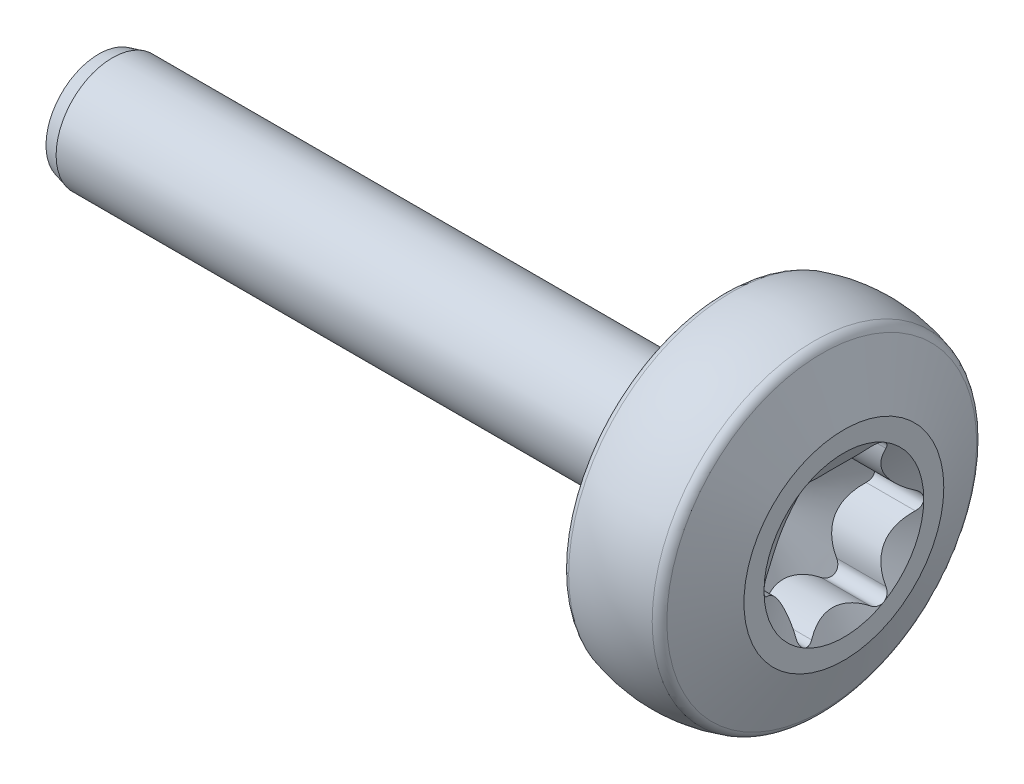
SolidWorks part; units mm, degrees
material "Alloy Steel"
ref_plane "Front Plane" through (0, 0, 0) normal (0, 0, 1) x (1, 0, 0)
ref_plane "Top Plane" through (0, 0, 0) normal (0, 1, 0) x (1, 0, 0)
ref_plane "Right Plane" through (0, 0, 0) normal (1, 0, 0) x (0, 0, -1)
sketch "Sketch1" plane through (0, 0, 0) normal (0, 0, 1) x (1, 0, 0)
  line L0 (-7.5819, 0) -> (7.5819, 0) construction
  line L1 (-7.5819, 1.7526) -> (-7.5819, -1.7526) construction
  line L2 (5.1181, 3.429) -> (5.1181, -3.429) construction
  line L3 (7.5819, 1.6256) -> (7.5819, -1.6256) construction
  line L4 (-8.0147, 1.8973) -> (-7.4298, 0.8843) construction
  line L5 (-7.4298, 0.8843) -> (-8.5996, 0.8843) construction
  line L6 (-8.5996, 0.8843) -> (-8.0147, 1.8973) construction
  line L7 (-8.5996, 0.8843) -> (-8.6831, 0.7396) construction
  line L8 (-8.6831, 0.7396) -> (-7.3463, 0.7396) construction
  line L9 (-7.3463, 0.7396) -> (-7.4298, 0.8843) construction
  line L10 (-8.0983, 1.7526) -> (-7.9312, 1.7526) construction
  line L11 (-8.0147, 1.8973) -> (-8.0147, 1.7526) construction
  line L12 (-8.0147, 0.8843) -> (-8.0147, 0.7396) construction
  point P11 (5.1181, 0)
  point P12 (-7.5819, 1.1477)
  dimension "Screw Size" = 3.5052
  dimension "Torx Diameter" = 3.2512
  dimension "Head Diameter" = 6.858
  dimension "Head Height" = 2.4638
  dimension "Length" = 12.7
  dimension "Thread ID" = 2.2954
  dimension "Approximate Thread Pitch" = 1.3368
  dimension "D1" = 0.1671
sketch "Sketch2" plane through (0, 0, 0) normal (0, 0, 1) x (1, 0, 0)
  line L0 (-7.5819, 0) -> (7.5819, 0)
  line L1 (7.5819, 0) -> (7.5819, 2.0336)
  line L2 (-7.5819, 0) -> (-7.5819, 1.1477)
  line L3 (-7.5819, 1.1477) -> (5.0419, 1.1477)
  line L6 (5.0419, 1.1477) -> (5.0419, 1.851)
  line L9 (-7.5819, 0) -> (-22.7457, 0) construction
  line L10 (5.0419, 1.851) -> (5.0419, 2.5543) construction
  line L11 (7.5819, 1.6256) -> (7.5819, 2.0336) construction
  line L12 (5.0419, 2.5543) -> (5.0419, 3.2576) construction
  line L14 (7.5819, 3.2576) -> (5.1181, 3.2576) construction
  line L15 (5.1181, 3.2576) -> (5.1181, 1.1477) construction
  line L17 (5.1181, 3.2576) -> (5.1181, 1.9272)
  line L18 (5.1181, 3.429) -> (5.1181, -3.429) construction
  line L19 (7.5819, 1.6256) -> (7.5819, -1.6256) construction
  line L20 (7.5819, 2.0336) -> (7.5819, 2.4416) construction
  line L21 (7.5819, 2.4416) -> (7.5819, 2.8496) construction
  line L22 (7.5819, 2.8496) -> (7.5819, 3.2576) construction
  line L23 (7.5819, 2.0336) -> (7.0891, 3.2576)
  arc A6 (7.0891, 3.2576) -> (5.1181, 3.2576) centre (6.1036, 0.5108) ccw
  arc A7 (5.1181, 1.9272) -> (5.08, 1.8891) centre (5.08, 1.9272) cw
  arc A8 (5.08, 1.8891) -> (5.0419, 1.851) centre (5.08, 1.851) ccw
  point P14 (6.1036, 3.429)
  dimension "D1" = 6.5151
  dimension "D2" = 0.0762
  dimension "D3" = 1.971
revolve "Revolve1" add sketch "Sketch2" angle 360 about L9
sketch "Sketch12" plane through (0, 0, 0) normal (0, 0, 1) x (1, 0, 0)
  line L0 (7.5819, 1.6256) -> (6.581, 1.6256)
  line L1 (6.581, 1.6256) -> (5.6424, 0)
  line L2 (-7.5819, 0) -> (7.5819, 0) construction
  line L3 (5.6424, 0) -> (7.5819, 0)
  line L4 (7.5819, 0) -> (7.5819, 1.6256)
  dimension "D1" = 60
  dimension "D2" = 1.0009
revolve "Cut-Revolve3" cut sketch "Sketch12" angle 360 about L0
sketch "Sketch3" plane through (7.5819, 0, 0) normal (1, 0, 0) x (0, 0, -1)
  line L0 (1.2192, 0) -> (1.4224, 0) construction
  line L1 (1.4224, 0) -> (1.6256, 0) construction
  line L2 (-0.8128, 1.4078) -> (0, 0) construction
  line L3 (0, 0) -> (0.8128, 1.4078) construction
  line L4 (0.8128, 1.4078) -> (-0.8128, 1.4078) construction
  circle A0 centre (0, 0) radius 1.6256 construction
  circle A1 centre (0, 0) radius 1.4224 construction
  circle A2 centre (0, 0) radius 1.2192 construction
  circle A51 centre (0, 0) radius 2.0336
  arc A54 (1.5122, -0.1823) -> (1.6256, 0) centre (1.4224, 0) ccw
  arc A55 (-0.5983, 1.4008) -> (0.5983, 1.4008) centre (0, 2.2957) ccw
  arc A56 (-0.5983, 1.4008) -> (-0.8128, 1.4078) centre (-0.7112, 1.2318) ccw
  arc A57 (1.5122, -0.1823) -> (0.914, -1.2185) centre (1.9881, -1.1478) ccw
  arc A58 (0.8128, 1.4078) -> (0.5983, 1.4008) centre (0.7112, 1.2318) ccw
  arc A59 (0.914, 1.2185) -> (0.8128, 1.4078) centre (0.7112, 1.2318) ccw
  arc A60 (0.8128, -1.4078) -> (0.914, -1.2185) centre (0.7112, -1.2318) ccw
  arc A61 (0.914, 1.2185) -> (1.5122, 0.1823) centre (1.9881, 1.1478) ccw
  arc A62 (1.6256, 0) -> (1.5122, 0.1823) centre (1.4224, 0) ccw
  arc A63 (0.5983, -1.4008) -> (0.8128, -1.4078) centre (0.7112, -1.2318) ccw
  arc A76 (0.5983, -1.4008) -> (-0.5983, -1.4008) centre (0, -2.2957) ccw
  arc A77 (-0.8128, -1.4078) -> (-0.5983, -1.4008) centre (-0.7112, -1.2318) ccw
  arc A78 (-0.914, -1.2185) -> (-0.8128, -1.4078) centre (-0.7112, -1.2318) ccw
  arc A79 (-0.914, -1.2185) -> (-1.5122, -0.1823) centre (-1.9881, -1.1478) ccw
  arc A80 (-1.6256, 0) -> (-1.5122, -0.1823) centre (-1.4224, 0) ccw
  arc A81 (-1.5122, 0.1823) -> (-1.6256, 0) centre (-1.4224, 0) ccw
  arc A82 (-1.5122, 0.1823) -> (-0.914, 1.2185) centre (-1.9881, 1.1478) ccw
  arc A83 (-0.8128, 1.4078) -> (-0.914, 1.2185) centre (-0.7112, 1.2318) ccw
  point P20 (0, 1.2192)
  point P58 (0, 0)
  point P72 (0, 0)
  dimension "D1" = 2.4384
  dimension "D2" = 6
extrude "Boss-Extrude1" add sketch "Sketch3" against normal up to surface (1.0601 mm away)
sketch "Sketch4" plane through (7.5819, 0, 0) normal (1, 0, 0) x (0, 0, -1)
  circle A0 centre (0, 0) radius 1.6256
extrude "Cut-Extrude2" cut sketch "Sketch4" against normal through all draft 60
fillet "Fillet1" radius 0.2464 2 edges at (5.1181, 0, -3.2576) (7.0891, 0, -3.2576)
chamfer "Chamfer1" distance 0.2807 angle 15 1 edges at (-7.5819, 0, -1.1477) first distance on face at (-7.5819, 0, -1.1477)
split "Split1" [suppressed] bodies to split 106
sketch "Sketch9" [suppressed] plane through (0, 0, 0) normal (0, 0, 1) x (1, 0, 0)
  line L0 (-7.5819, 1.7526) -> (-7.5819, 0)
  line L1 (-7.5819, 0) -> (5.0419, 0)
  line L2 (-7.5819, 0) -> (7.5819, 0) construction
  line L3 (5.0419, 0) -> (5.0419, 1.7526)
  line L5 (5.0419, 1.7526) -> (-7.5819, 1.7526)
revolve "Revolve2" [suppressed] add sketch "Sketch9" angle 360 about L0
sketch "Sketch5" [suppressed] plane through (-7.5819, 0, 0) normal (-1, 0, 0) x (0, 0, 1)
  circle A0 centre (0, 0) radius 1.1477
curve "Helix/Spiral1" [suppressed] pitch 1.3368 height 15.3737 turns 11.5
sketch "Sketch7" [suppressed] plane through (0, 0, 0) normal (0, 0, 1) x (1, 0, 0)
  line L0 (-7.5819, 1.1477) -> (-7.8135, 1.2097) construction
  line L1 (-7.8135, 1.2097) -> (-7.959, 1.7526) construction
  line L2 (-8.0983, 1.7526) -> (-7.9312, 1.7526) construction
  line L3 (-7.959, 1.7526) -> (-8.0704, 1.7526) construction
  line L4 (-8.0704, 1.7526) -> (-8.2159, 1.2097)
  line L5 (-8.2159, 1.2097) -> (-8.4475, 1.1477)
  line L6 (-8.5996, 0.8843) -> (-8.0147, 1.8973) construction
  line L7 (-8.4475, 1.1477) -> (-8.4475, 0.8843) construction
  line L8 (-7.4298, 0.8843) -> (-8.5996, 0.8843) construction
  line L9 (-8.4475, 0.8843) -> (-7.5819, 0.8843) construction
  line L10 (-7.5819, 0.8843) -> (-7.5819, 1.1477) construction
  line L11 (-8.0147, 0.8843) -> (-8.0147, 0.7396) construction
  line L12 (-8.6831, 0.7396) -> (-8.7667, 0.8843) construction
  line L13 (-8.7667, 0.8843) -> (-9.3515, 1.8973) construction
  line L14 (-8.0147, 1.8973) -> (-7.4298, 0.8843) construction
  line L15 (-7.3463, 0.7396) -> (-7.4298, 0.8843) construction
  line L16 (-8.9187, 1.1477) -> (-8.4475, 1.1477)
  line L19 (-8.9187, 1.1477) -> (-9.1504, 1.2097)
  line L20 (-9.1504, 1.2097) -> (-9.2958, 1.7526)
  line L22 (-9.2958, 1.7526) -> (-9.2958, 1.8973)
  line L23 (-9.2958, 1.8973) -> (-8.0704, 1.8973)
  line L24 (-8.0704, 1.8973) -> (-8.0704, 1.7526)
  point P33 (-4.6169, -1.7526)
  dimension "D3" = 0.1114
  dimension "D1" = 15
  dimension "D2" = 15
  dimension "D4" = 3.3421
sweep "Cut-Sweep1" [suppressed] cut profiles "Sketch7" path "Helix/Spiral1"
combine bodies "Combine1" [suppressed] operation type add bodies to combine 107 113 119
sketch "Sketch13" [suppressed] plane through (5.0419, 0, 0) normal (-1, 0, 0) x (0, 0, 1)
  circle A0 centre (0, 0) radius 1.7272
  point P3 (0, 1.7272)
  dimension "D1" = 0.0254
extrude "Boss-Extrude2" [suppressed] add sketch "Sketch13" along normal through all draft 45
sketch "Sketch14" [suppressed] plane through (-7.5819, 0, 0) normal (-1, 0, 0) x (0, 0, 1)
  circle A2 centre (0, 0) radius 1.1223
  point P1 (0, 1.1223)
  dimension "D1" = 0.0254
extrude "Cut-Extrude3" [suppressed] cut sketch "Sketch14" against normal up to next draft 45 flip side to cut draft outward yes
equation "\"Thread ID@Sketch1\"=\"Screw Size@Sketch1\"-(\"Approximate Thread Pitch@Sketch1\"*.905)"
equation "\"D1@Sketch3\"=\"Torx Diameter@Sketch1\"*.75"
equation "\"D4@Helix/Spiral1\"=\"Approximate Thread Pitch@Sketch1\""
equation "\"D3@Helix/Spiral1\"=\"Length@Sketch1\"+2*\"Approximate Thread Pitch@Sketch1\""
equation "\"D1@Sketch1\"=\"Approximate Thread Pitch@Sketch1\"/8"
equation "\"D3@Sketch7\"=\"Approximate Thread Pitch@Sketch1\"/12"
equation "\"D4@Sketch7\"=\"Approximate Thread Pitch@Sketch1\"*2.5"
equation "\"D2@Sketch12\"= \"Head Height@Sketch1\" * .40625"
equation "\"D1@Sketch2\"=\"Head Diameter@Sketch1\"*.95"
equation "\"D3@Sketch2\"=\"Head Height@Sketch1\"*.8"
equation "\"D1@Fillet1\"=\"Head Height@Sketch1\" * .1"
equation "\"D1@Chamfer1\"=\"approximate thread pitch@sketch1\"*.21"
